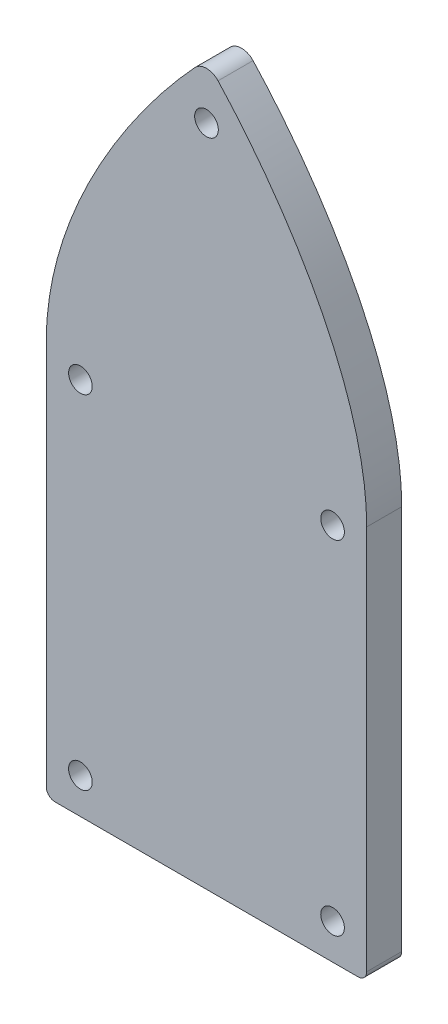
SolidWorks part; units mm, degrees
ref_plane "Front Plane" through (0, 0, 0) normal (0, 0, 1) x (1, 0, 0)
ref_plane "Top Plane" through (0, 0, 0) normal (0, 1, 0) x (1, 0, 0)
ref_plane "Right Plane" through (0, 0, 0) normal (1, 0, 0) x (0, 0, -1)
sketch "Sketch1" plane through (0, 0, 0) normal (0, 0, 1) x (1, 0, 0)
  line L0 (0, 72) -> (0, 0) construction
  line L1 (12, 0) -> (-12, 0)
  line L2 (-12, 0) -> (-12, 42)
  line L3 (-12, 42) -> (-11, 56)
  line L4 (-11, 56) -> (-7, 66)
  line L5 (-7, 66) -> (-1.7, 72)
  line L6 (-1.7, 72) -> (1.7, 72)
  line L7 (7, 66) -> (1.7, 72)
  line L8 (11, 56) -> (7, 66)
  line L9 (12, 42) -> (11, 56)
  line L10 (12, 0) -> (12, 42)
  dimension "D1" = 3.4
  dimension "D2" = 5.3
  dimension "D3" = 6
  dimension "D4" = 4
  dimension "D5" = 10
  dimension "D6" = 1
  dimension "D7" = 14
  dimension "D8" = 42
sketch "Sketch2" plane through (0, 0, 0) normal (0, 0, 1) x (1, 0, 0)
  line L0 (0, -1.2) -> (0, 80.8) construction
  line L1 (-18.3, -1.2) -> (18.3, -1.2)
  line L2 (18.3, -1.2) -> (18.3, 43.8)
  line L4 (12, 0) -> (-12, 0) construction
  line L5 (12, 0) -> (12, 42) construction
  line L6 (0, 80.8) -> (-4.6292, 85.4292) construction
  line L7 (0, 80.8) -> (-5.4755, 80.8) construction
  line L8 (-18.3, -1.2) -> (-18.3, 43.8)
  spline S0 degree 3 poles (18.3, 43.8) (18.3, 58.8) (6.364, 74.436) (0, 80.8) knots 0 0 0 0 1 1 1 1
  spline S1 degree 3 poles (-18.3, 43.8) (-18.3, 58.8) (-6.364, 74.436) (0, 80.8) knots 0 0 0 0 1 1 1 1
  dimension "D6" = 45
  dimension "D7" = 27
  dimension "D1" = 82
  dimension "D2" = 1.2
  dimension "D3" = 6.3
  dimension "D4" = 45
  dimension "D5" = 45
extrude "Boss-Extrude1" add sketch "Sketch2" along normal blind 4
hole_wizard "CBORE for M5 Hex Head Bolt1" positions "Sketch3" profile "Sketch4" counterbore size "M5" standard "DIN" end condition through all
sketch "Sketch3" plane through (0, 0, 0) normal (0, 0, -1) x (-1, 0, 0)
  point P0 (14.4, 42.0178)
  point P3 (14.4, 2.8635)
  point P6 (-14.4, 2.8635)
  point P9 (-14.4, 42.0178)
  point P12 (0, 74.6)
sketch "Sketch4" plane through (-14.4, 42.0178, 0) normal (1, 0, 0) x (0, 1, 0)
  line L0 (0, 0) -> (0, 4)
  line L1 (0, 4) -> (1.35, 4)
  line L3 (1.35, 4) -> (1.35, 2)
  line L4 (1.35, 2) -> (2.5, 2)
  line L5 (2.5, 2) -> (2.5, 0)
  line L7 (2.5, 0) -> (0, 0)
  line L11 (0, -6.35) -> (0, 107.95) construction
  dimension "Thru Hole Dia." = 2.7
  dimension "Thru Hole Depth" = 4
  dimension "C'Bore Dia." = 5
  dimension "C'Bore Depth" = 2
ref_plane "Plane1" through (7, 0, 0) normal (1, 0, 0) x (0, 0, -1)
sketch "Sketch6" plane through (7, 0, 0) normal (1, 0, 0) x (0, 0, -1)
  line L0 (0, 44.8) -> (5.5, 44.8)
  line L1 (0, -1.2) -> (0, 43.8) construction
  line L2 (5.5, 34.8) -> (0, 34.8)
  line L3 (0, 34.8) -> (0, 44.8)
  line L4 (5.5, 34.8) -> (5.5, 44.8) construction
  line L6 (-4, 43.8) -> (0, 43.8) construction
  arc A0 (5.5, 44.8) -> (5.5, 34.8) centre (5.5, 39.8) cw
  circle A1 centre (5.5, 39.8) radius 1.75
  dimension "D1" = 3.5
  dimension "D2" = 5
  dimension "D3" = 5.5
  dimension "D4" = 1
extrude "Boss-Extrude2" add sketch "Sketch6" against normal blind 4
fillet "Fillet1" radius 5.5 2 edges at (5, 34.8, 0) (5, 44.8, 0)
mirror "Mirror1" about plane through (0, 0, 0) normal (1, 0, 0) of "Fillet1", "Boss-Extrude2"
fillet "Fillet2" radius 1.8 1 edges at (0, 80.8, 2)
fillet "Fillet3" radius 1 2 edges at (18.3, -1.2, 2) (-18.3, -1.2, 2)
